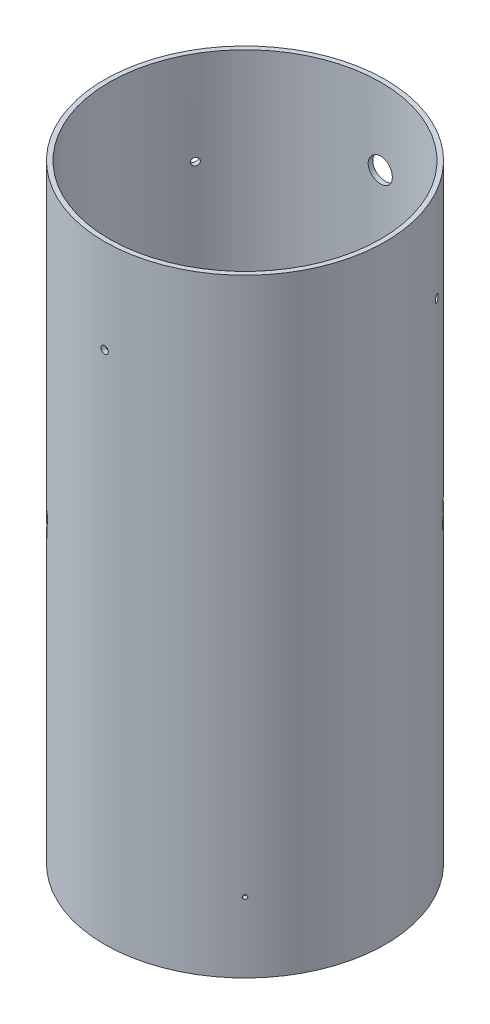
SolidWorks part; units mm, degrees
material "A-Glass Fiber"
ref_plane "Front Plane" through (0, 0, 0) normal (0, 0, 1) x (1, 0, 0)
ref_plane "Top Plane" through (0, 0, 0) normal (0, 1, 0) x (1, 0, 0)
ref_plane "Right Plane" through (0, 0, 0) normal (1, 0, 0) x (0, 0, -1)
sketch "Sketch1" plane through (0, 0, 0) normal (0, 1, 0) x (1, 0, 0)
  circle A0 centre (0, 0) radius 76.1746
  circle A1 centre (0, 0) radius 73.66
  dimension "D1" = 152.3492
  dimension "D2" = 147.32
extrude "Boss-Extrude1" add sketch "Sketch1" along normal blind 330.2
sketch "Sketch4" plane through (0, 0, 0) normal (0, 0, 1) x (1, 0, 0)
  line L0 (-76.1746, 0) -> (76.1746, 0) construction
  line L1 (76.1746, 330.2) -> (-76.1746, 330.2) construction
  line L2 (0, 330.2) -> (0, 0) construction
  line L3 (73.66, 330.2) -> (-73.66, 330.2) construction
  point P0 (0, 41.275)
  point P3 (0, 288.925)
  dimension "D1" = 41.275
  dimension "D2" = 41.275
hole_wizard "1/2 Clearance Hole5" positions "Sketch16" profile "Sketch17" hole size "1/2" standard "ANSI Inch"
sketch "Sketch16" plane through (0, 0, 0) normal (0, 0, 1) x (1, 0, 0)
  point P0 (0, 288.925)
sketch "Sketch17" plane through (0, 288.925, 0) normal (1, 0, 0) x (0, -1, 0)
  line L0 (0, 0) -> (0, 80.1345)
  line L1 (0, 80.1345) -> (6.5481, 76.2)
  line L2 (6.5481, 76.2) -> (6.5481, 0)
  line L5 (6.5481, 0) -> (0, 0)
  line L10 (0, 80.1345) -> (-6.5481, 76.2) construction
  line L11 (0, -6.35) -> (0, 107.95) construction
  dimension "Hole Dia." = 13.0962
  dimension "Hole Depth" = 76.2
  dimension "Drill Angle" = 118
hole_wizard "1/2 Clearance Hole7" positions "Sketch20" profile "Sketch21" hole size "1/2" standard "ANSI Inch"
sketch "Sketch20" plane through (0, 0, 0) normal (0, 0, 1) x (1, 0, 0)
  point P0 (0, 41.275)
sketch "Sketch21" plane through (0, 41.275, 0) normal (1, 0, 0) x (0, -1, 0)
  line L0 (0, 0) -> (0, 80.1345)
  line L1 (0, 80.1345) -> (6.5481, 76.2)
  line L2 (6.5481, 76.2) -> (6.5481, 0)
  line L5 (6.5481, 0) -> (0, 0)
  line L10 (0, 80.1345) -> (-6.5481, 76.2) construction
  line L11 (0, -6.35) -> (0, 107.95) construction
  dimension "Hole Dia." = 13.0962
  dimension "Hole Depth" = 76.2
  dimension "Drill Angle" = 118
ref_plane "Plane1" through (0, 0, 0) normal (-0.7071, 0, 0.7071) x (0.7071, 0, 0.7071)
sketch "Sketch23" plane through (0, 0, 0) normal (-0.7071, 0, 0.7071) x (0.7071, 0, 0.7071)
  line L0 (0, 0) -> (0, 330.2) construction
  line L1 (73.66, 330.2) -> (-73.66, 330.2) construction
  line L2 (-76.1746, 165.1) -> (76.1746, 165.1) construction
  line L3 (76.1746, 0) -> (76.1746, 330.2) construction
  circle A1 centre (0, 38.1) radius 1.0922
  point P12 (0, 165.1)
  dimension "D2" = 127
extrude "Shear Scrrews" cut sketch "Sketch23" against normal through all
pattern_circular "CirPattern1" count 4 over 360 about axis through (0, 330.2, 0) along (0, -1, 0) of "Shear Scrrews"
hole_wizard "Ø4.0 (4) Diameter Hole1" positions "Sketch24" profile "Sketch25" hole size "Ø4.0" standard "ANSI Metric"
sketch "Sketch24" plane through (0, 0, 0) normal (0, 0, 1) x (1, 0, 0)
  line L0 (76.1746, 330.2) -> (-76.1746, 330.2) construction
  point P0 (0, 279.4)
  dimension "D1" = 50.8
sketch "Sketch25" plane through (0, 279.4, 0) normal (1, 0, 0) x (0, 1, 0)
  line L0 (0, 0) -> (0, 90.1017)
  line L1 (0, 90.1017) -> (2, 88.9)
  line L2 (2, 88.9) -> (2, 0)
  line L5 (2, 0) -> (0, 0)
  line L10 (0, 90.1017) -> (-2, 88.9) construction
  line L11 (0, -6.35) -> (0, 107.95) construction
  dimension "Hole Dia." = 4
  dimension "Hole Depth" = 88.9
  dimension "Drill Angle" = 118
pattern_circular "CirPattern2" count 3 over 360 about axis through (0, 330.2, 0) along (0, 1, 0) of "Ø4.0 (4) Diameter Hole1"
ref_plane "Camera Cutout Plane" through (0, 0, 0) normal (0.7071, 0, -0.7071) x (0, -1, 0)
sketch "Sketch26" plane through (0, 0, 0) normal (0.7071, 0, -0.7071) x (0, -1, 0)
  line L0 (-330.2, 0) -> (0, 0) construction
  line L1 (-174.625, -5) -> (-167.625, -5)
  line L2 (-174.625, -5) -> (-174.625, 5)
  line L3 (-174.625, 5) -> (-167.625, 5)
  line L4 (-167.625, -5) -> (-167.625, 5)
  line L5 (-174.625, -5) -> (-167.625, 5) construction
  line L6 (-174.625, 5) -> (-167.625, -5) construction
  line L7 (-330.2, 76.1746) -> (-330.2, -76.1746) construction
  circle A0 centre (-158.735, 0) radius 2.75
  point P0 (-171.125, 0)
  dimension "D4" = 5.5
  dimension "D1" = 7
  dimension "D2" = 10
  dimension "D3" = 155.575
  dimension "D5" = 8.89
extrude "Upwards Camera Cutout" cut sketch "Sketch26" along normal through all
sketch "Sketch27" plane through (0, 0, 0) normal (0.7071, 0, -0.7071) x (0, -1, 0)
  line L0 (-330.2, 0) -> (0, 0) construction
  line L1 (-155.575, 5) -> (-162.575, 5)
  line L2 (-155.575, 5) -> (-155.575, -5)
  line L3 (-155.575, -5) -> (-162.575, -5)
  line L4 (-162.575, 5) -> (-162.575, -5)
  line L5 (-155.575, 5) -> (-162.575, -5) construction
  line L6 (-155.575, -5) -> (-162.575, 5) construction
  line L8 (0, -76.1746) -> (0, 76.1746) construction
  circle A0 centre (-171.465, 0) radius 2.75
  point P0 (-159.075, 0)
  dimension "D4" = 5.5
  dimension "D1" = 7
  dimension "D2" = 10
  dimension "D3" = 8.89
  dimension "D5" = 155.575
extrude "Downwards Camera Cutout" cut sketch "Sketch27" against normal through all
ref_plane "Camera Side Hole Plane" through (0, 0, 0) normal (0.7567, 0, -0.6537) x (0, -1, 0)
sketch "Sketch28" plane through (0, 0, 0) normal (0.7567, 0, -0.6537) x (0, -1, 0)
  line L0 (-330.2, 0) -> (0, 0) construction
  line L1 (-162.575, -10.5216) -> (-162.575, -0.5482) construction
  circle A0 centre (-166.385, 0) radius 2.75
  dimension "D1" = 5.5
  dimension "D2" = 3.81
extrude "Cut-Extrude4" cut sketch "Sketch28" against normal through all
pattern_circular "CirPattern3" count 2 every 8.407 about axis through (0, 0, 0) along (0, 1, 0) of "Cut-Extrude4"
sketch "Sketch29" plane through (0, 0, 0) normal (0.7567, 0, -0.6537) x (0, -1, 0)
  line L0 (-330.2, 0) -> (0, 0) construction
  line L1 (-167.625, 10.3381) -> (-167.625, 0.3647) construction
  circle A0 centre (-163.815, 0) radius 2.75
  dimension "D1" = 5.5
  dimension "D2" = 3.81
extrude "Cut-Extrude5" cut sketch "Sketch29" along normal through all
pattern_circular "CirPattern4" count 2 every 8.407 about axis through (0, 330.2, 0) along (0, 1, 0) of "Cut-Extrude5"
equation "\"Mid_Coupler_Length\" = 13in"
equation "\"D1@Boss-Extrude1\"=\"Mid_Coupler_Length\""
equation "\"Shear_Screw_Coupler_Location\" = 4.5in"
equation "\"Shear_Screw_Diameter\" = 0.086in"
equation "\"D2@Sketch23\"=\"Shear_Screw_Coupler_Location\"+0.5"
equation "\"Mid_Tube_Length\" = 1in"
equation "\"Bodytube_OD\" = 6.17in"
equation "\"Bodytube_ID\" = 5.998in"
equation "\"Camera_Cutout_Width\"=10mm"
equation "\"Camera_Cutout_Height\"=7mm"
equation "\"Fwd_Tube_Length\" = 40in"
equation "\"BKHD_Screw_Diam\"= 3.5mm"
equation "\"Fwd_BKHD_From_Top\" = 18in"
equation "\"Motor_OD\" = 4in"
equation "\"Aft_Section_Length\"= 39in"
equation "\"AB_Coupler_OD_Length\"= 1in"
equation "\"AB_Coupling_Section_Length\"= 0.375in"
equation "\"AB_Coupler_Length\"= \"AB_Coupler_OD_Length\" + \"AB_Coupling_Section_Length\" * 2"
equation "\"Cutout_Angle\" = 80"
equation "\"AB_Paddle_Height\" = 0.375in"
equation "\"AB_Coupler_Num_Screws\"= 4"
equation "\"AB_BKHD_Thickness\" = 0.375in"
equation "\"AB_Mount_From_Bottom\" = 23.175in"
equation "\"Num_Cutouts\" = 3"
equation "\"AB_Coupler_OD\"= 6.17in"
equation "\"AB_Coupler_ID\"= 5.75in"
equation "\"AB_Coupler_Surface_Diameter\"= 5.998in"
equation "\"AB_Coupling_Screw_Diameter\"= 0.15748in"
equation "\"AB_Central_Bushing_Length\" = .4724in"
equation "\"Lead_Screw_Dist\" = 3.4in"
equation "\"Lead_Screw_Diam\" = 0.386in"
equation "\"Lead_Screw_Length\" = (\"Mid_Coupler_Length\" + 2*0.375in + 2*0.5in)"
equation "\"Paddle_Pin_Offset\" = .25in"
equation "\"Paddle_Pin_Radius\" = 2.25in"
equation "\"SS_Paddle_Pin_Radius\" = 2.25*0.66in"
equation "\"Paddle_Gear_OD\" = 3.2in"
equation "\"Drive_Gear_OD\" = 1.7in"
equation "\"Fin_Thickness\"= .118in"
equation "\"Guiderail_Cutout_Diameter\"= 1.5in"
equation "\"DB9_Hole_Dist\" = 25mm"
equation "\"DB9_Relief_Width\" = 0.47in"
equation "\"DB9_Relief_Hole_Offset\" = 0.09in"
equation "\"Airbrakes_Wire_Hole_Dia\" = .25in"
equation "\"Airbrakes_Wire_Hole_Dist\" = 1.1in"
equation "\"Servo_Gear_Offset\" = 0.5in"
equation "\"FWD_Shear_Screw_Dist\" = 1.5in"
equation "\"Camera_Screw_Dia\" = 0.216535"
equation "\"Camera_Hole_Angle\" = atn ( 2 / 3 * tan ( 12.5deg ) )"
equation "\"D1@Sketch26\"=\"Camera_Cutout_Height\""
equation "\"D2@Sketch26\"=\"Camera_Cutout_Width\""
equation "\"D3@Sketch26\"=6.125"
equation "\"D1@Sketch27\"=\"Camera_Cutout_Height\""
equation "\"D2@Sketch27\"=\"Camera_Cutout_Width\""
equation "\"D1@Sketch28\"=\"Camera_Screw_Dia\""
equation "\"D2@CirPattern3\"=\"Camera_Hole_Angle\""
equation "\"D1@Sketch29\"=\"Camera_Screw_Dia\""
equation "\"D2@CirPattern4\"=\"Camera_Hole_Angle\""
equation "\"Coupler_OD\" = 5.998"
equation "\"D1@Sketch1\"=\"Coupler_OD\""
equation "\"Coupler_ID\" = 5.8"
equation "\"D2@Sketch1\"=\"Coupler_ID\""
